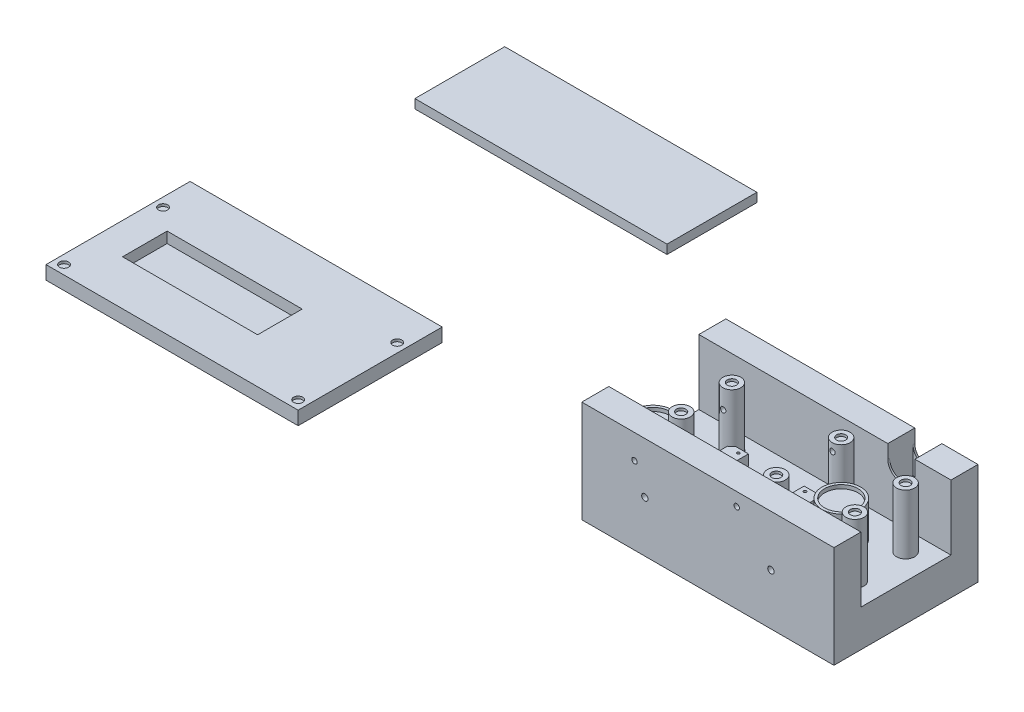
SolidWorks part; units mm, degrees
ref_plane "Front Plane" through (0, 0, 0) normal (0, 0, 1) x (1, 0, 0)
ref_plane "Top Plane" through (0, 0, 0) normal (0, 1, 0) x (1, 0, 0)
ref_plane "Right Plane" through (0, 0, 0) normal (1, 0, 0) x (0, 0, -1)
sketch "Sketch1" plane through (0, 0, 0) normal (0, 1, 0) x (1, 0, 0)
  line L1 (-125, -50) -> (125, -50)
  line L2 (-125, -50) -> (-125, 50)
  line L3 (-125, 50) -> (125, 50)
  line L4 (125, -50) -> (125, 50)
  line L5 (0, 50) -> (0, -50) construction
  line L6 (-125, 0) -> (125, 0) construction
  line L7 (-87.9863, 22.88) -> (-72.79, 22.88)
  line L8 (-91.88, 19.2734) -> (-91.88, -19.2734)
  line L9 (-87.9863, -22.88) -> (-72.79, -22.88)
  line L10 (-72.79, 22.88) -> (-72.79, -22.88)
  line L11 (-10.96, 22.88) -> (8.13, 22.88)
  line L12 (-10.96, 22.88) -> (-10.96, -22.88)
  line L13 (-10.96, -22.88) -> (8.13, -22.88)
  line L14 (8.13, 22.88) -> (8.13, -22.88)
  circle A0 centre (-96.485, 28.15) radius 10
  circle A1 centre (-96.485, -28.15) radius 10
  circle A2 centre (96.485, 28.15) radius 10
  circle A3 centre (96.485, -28.15) radius 10
  circle A4 centre (48.387, 4.8142) radius 21.5
  circle A5 centre (48.387, 4.8142) radius 18.55
  circle A6 centre (-96.485, 28.15) radius 5.17
  circle A7 centre (-96.485, -28.15) radius 5.17
  circle A8 centre (96.485, 28.15) radius 5.17
  circle A9 centre (96.485, -28.15) radius 5.17
  circle A10 centre (-96.485, 28.15) radius 10.5
  circle A11 centre (-96.485, -28.15) radius 10.5
  circle A12 centre (96.485, 28.15) radius 10.5
  circle A13 centre (96.485, -28.15) radius 10.5
  point P0 (0, 0)
  dimension "D3" = 20
  dimension "D6" = 53.46
  dimension "D8" = 43
  dimension "D9" = 37.1
  dimension "D15" = 10.34
  dimension "D16" = 21
  dimension "D17" = 10.34
  dimension "D1" = 250
  dimension "D2" = 100
  dimension "D4" = 192.97
  dimension "D5" = 56.3
  dimension "D7" = 58.31
  dimension "D10" = 19.09
  dimension "D11" = 45.76
  dimension "D12" = 33.12
  dimension "D13" = 114.04
  dimension "D14" = 19.09
extrude "Boss-Extrude1" add sketch "Sketch1" against normal blind 41 contours L1 L4 L3 L2
extrude "Boss-Extrude2" add sketch "Sketch1<4>" along normal blind 12 contours A1 L9 L10 L7 A0 L8 | L14 L11 L12 L13 region at (-82.1271, 0, 0) region at (-1.415, 0, 0)
sketch "Sketch1<4>" plane through (0, 0, 0) normal (0, 1, 0) x (1, 0, 0) same geometry as "Sketch1"
extrude "Boss-Extrude3" add sketch "Sketch1<5>" along normal blind 39 contours A4 A5 region at (27.4951, 0, -4.8142)
sketch "Sketch1<5>" plane through (0, 0, 0) normal (0, 1, 0) x (1, 0, 0) same geometry as "Sketch1"
extrude "Boss-Extrude4" add sketch "Sketch1<6>" along normal blind 34.9 contours A5
sketch "Sketch1<6>" plane through (0, 0, 0) normal (0, 1, 0) x (1, 0, 0) same geometry as "Sketch1"
extrude "Cut-Extrude1" cut sketch "Sketch1<9>" against normal blind 5 contours L8 A11 L9 A1 | A1 A7 | A7 | L7 A10 L8 A0 | A0 A6 | A6 | L9 A11 L8 A1 | L8 A10 L7 A0 region at (-86.582, 0, -25.3288) region at (-89.5989, 0, -20.7343) region at (-89.8817, 0, -21.0212) region at (-89.5989, 0, 20.7343) region at (-92.177, 0, 18.9935) region at (-89.8817, 0, 21.0212) region at (-96.485, 0, -28.15) region at (-96.485, 0, 28.15)
sketch "Sketch1<9>" plane through (0, 0, 0) normal (0, 1, 0) x (1, 0, 0) same geometry as "Sketch1"
extrude "Boss-Extrude7" add sketch "Sketch1<10>" along normal blind 66.2 contours A3 A9 | A9 | A2 A8 | A8 | A3 region at (86.7678, 0, -28.15) region at (86.7678, 0, 28.15) region at (96.485, 0, -28.15) region at (96.485, 0, 28.15)
sketch "Sketch1<10>" plane through (0, 0, 0) normal (0, 1, 0) x (1, 0, 0) same geometry as "Sketch1"
extrude "Boss-Extrude8" add sketch "Sketch1<11>" along normal blind 66.2 and the other way up to surface (5 mm away) separate body contours A1 A7 | A7 | A6 | A0 A6 region at (-89.8817, 0, -21.0212) region at (-89.8817, 0, 21.0212) region at (-96.485, 0, -28.15) region at (-96.485, 0, 28.15) other way up to face at (-96.485, -5, -17.65)
sketch "Sketch1<11>" plane through (0, 0, 0) normal (0, 1, 0) x (1, 0, 0) same geometry as "Sketch1"
extrude "Cut-Extrude2" cut sketch "Sketch1<12>" against normal blind 2.75 from surface contours A7 | A6 | A9 | A8 starting at face at (-96.485, 66.2, -18.15)
sketch "Sketch1<12>" plane through (0, 0, 0) normal (0, 1, 0) x (1, 0, 0) same geometry as "Sketch1"
sketch "Sketch3" plane through (0, 12, 0) normal (0, 1, 0) x (1, 0, 0)
  circle A0 centre (-79.2548, 18.1338) radius 1.5
  circle A1 centre (-79.2548, 0.1338) radius 1.5
  circle A2 centre (-5.2548, 18.1338) radius 1.5
  circle A3 centre (-5.2548, 0.1338) radius 1.5
  dimension "D1" = 3
  dimension "D2" = 18
  dimension "D3" = 74
  dimension "D4" = 8.02
  dimension "D5" = 19.93
extrude "Cut-Extrude3" cut sketch "Sketch3" against normal blind 12
sketch "Sketch4" plane through (0, -41, 0) normal (0, -1, 0) x (1, 0, 0)
  line L1 (-120, 30) -> (-39.4754, 30)
  line L2 (-120, 30) -> (-120, -19.5)
  line L3 (-120, -19.5) -> (30, -19.5)
  line L4 (30, 30) -> (30, -19.5)
  line L5 (-125, 50) -> (-125, -50) construction
  line L6 (-125, 50) -> (125, 50) construction
  line L7 (-15.8404, 30) -> (30, 30)
  arc A0 (-15.8404, 30) -> (-39.4754, 30) centre (-27.6579, 30) ccw
  dimension "D1" = 150
  dimension "D2" = 49.5
  dimension "D3" = 20
  dimension "D4" = 5
extrude "Cut-Extrude4" cut sketch "Sketch4" against normal blind 31 contours L1 A0 L7 L4 L3 L2
sketch "Sketch5" plane through (-125, 0, 0) normal (-1, 0, 0) x (0, 0, 1)
  line L0 (-50, 0) -> (-50, -41)
  line L1 (-50, -41) -> (50, -41)
  line L2 (50, -41) -> (50, 0)
  line L3 (50, 0) -> (-50, 0)
extrude "Boss-Extrude9" add sketch "Sketch5" along normal blind 30
sketch "Sketch6" plane through (0, 0, 0) normal (0, 1, 0) x (1, 0, 0)
  line L0 (-130.5, -25.5) -> (-130.5, -47) construction
  line L1 (-155, -50) -> (125, -50) construction
  line L2 (-130.5, -25.5) -> (-155, -25.5) construction
  line L3 (-155, -50) -> (-155, 50) construction
  line L4 (-130.5, -25.5) -> (-152, -25.5) construction
  circle A0 centre (-130.5, -25.5) radius 21.5
  circle A1 centre (-130.5, -25.5) radius 18.55
  dimension "D1" = 43
  dimension "D2" = 37.1
  dimension "D3" = 3
  dimension "D4" = 3
extrude "Boss-Extrude10" add sketch "Sketch6" along normal blind 39
sketch "Sketch7" plane through (0, 0, 0) normal (0, 1, 0) x (1, 0, 0)
  circle A0 centre (-130.5, -25.5) radius 18.55
extrude "Boss-Extrude11" add sketch "Sketch7" along normal blind 35
sketch "Sketch8" plane through (-155, 0, 0) normal (-1, 0, 0) x (0, 0, 1)
  line L0 (4, 30.377) -> (4, -41) construction
  line L1 (4, 39) -> (4, 0) construction
  line L2 (-50, -41) -> (50, -41) construction
  line L3 (50, -41) -> (50, 0) construction
  line L4 (47, 20.3949) -> (47, -41) construction
  line L5 (47, 0) -> (47, 39) construction
  dimension "D1" = 46
  dimension "D2" = 3
sketch "Sketch10" plane through (0, 0, 0) normal (0, 1, 0) x (1, 0, 0)
  line L0 (-155, 0) -> (125, 0) construction
  line L1 (-155, -50) -> (-155, 50) construction
  line L2 (125, -50) -> (125, 50) construction
  line L3 (17, -36) -> (17, -46) construction
  line L4 (-155, -50) -> (125, -50) construction
  circle A0 centre (17, -36) radius 10
  circle A1 centre (17, 36) radius 10
  circle A2 centre (17, -36) radius 5.09
  circle A3 centre (17, 36) radius 5.09
  dimension "D1" = 20
  dimension "D4" = 10.18
  dimension "D2" = 4
  dimension "D3" = 108
extrude "Boss-Extrude12" add sketch "Sketch10" along normal blind 66.2
sketch "Sketch11" plane through (0, 0, 0) normal (0, 1, 0) x (1, 0, 0)
  circle A0 centre (17, -36) radius 5.17
  circle A1 centre (17, 36) radius 5.17
  dimension "D1" = 10.34
  dimension "D2" = 10.34
extrude "Boss-Extrude13" add sketch "Sketch11" along normal blind 63.45
sketch "Sketch9" plane through (0, 0, 50) normal (0, 0, 1) x (1, 0, 0)
  line L0 (-96.485, 66.2) -> (-96.485, 0) construction
  line L1 (-86.485, 66.2) -> (-106.485, 66.2) construction
  line L2 (-155, 0) -> (125, 0) construction
  line L3 (-96.485, 0) -> (-96.485, 45) construction
  line L4 (-96.485, 0) -> (-96.485, 57.6) construction
  line L5 (17, 66.2) -> (17, 0) construction
  line L6 (22.09, 66.2) -> (11.91, 66.2) construction
  line L7 (17, 0) -> (17, 57.6) construction
  circle A0 centre (-96.485, 45) radius 3
  circle A1 centre (17, 57.6) radius 3
  dimension "D2" = 6
  dimension "D5" = 6
  dimension "D1" = 45
  dimension "D3" = 57.6
  dimension "D4" = 57.6
extrude "Cut-Extrude5" cut sketch "Sketch9" against normal through all both and the other way through all
sketch "Sketch15" plane through (0, 0, 50) normal (0, 0, 1) x (1, 0, 0)
  line L0 (-155, 15.6) -> (125, 15.6) construction
  line L1 (-155, -41) -> (125, -41)
  line L2 (-155, -41) -> (-155, 72.2)
  line L3 (-155, 72.2) -> (125, 72.2)
  line L4 (125, -41) -> (125, 72.2)
  line L6 (-155, 15.6) -> (-85, 15.6) construction
  line L7 (-85, 15.6) -> (55, 15.6) construction
  circle A0 centre (-85, 15.6) radius 3.5
  circle A1 centre (55, 15.6) radius 3.5
  dimension "D5" = 7
  dimension "D6" = 7
  dimension "D1" = 113.2
  dimension "D2" = 280
  dimension "D3" = 70
  dimension "D4" = 140
extrude "Boss-Extrude17" add sketch "Sketch15" along normal blind 30
sketch "Sketch20" plane through (0, 0, 0) normal (0, 1, 0) x (1, 0, 0)
  line L0 (-605.7799, 235.3036) -> (-325.7799, 235.3036) construction
  line L1 (-605.7799, 285.3036) -> (-325.7799, 285.3036)
  line L2 (-605.7799, 285.3036) -> (-605.7799, 185.3036)
  line L3 (-605.7799, 185.3036) -> (-325.7799, 185.3036)
  line L4 (-325.7799, 285.3036) -> (-325.7799, 185.3036)
  circle A0 centre (-547.2649, 263.4536) radius 5.05
  circle A1 centre (-547.2649, 263.4536) radius 10.05
  circle A2 centre (-433.7799, 271.3036) radius 5.05
  circle A3 centre (-433.7799, 271.3036) radius 10.05
  circle A4 centre (-354.2949, 263.4536) radius 5.05
  circle A5 centre (-354.2949, 263.4536) radius 10.05
  circle A6 centre (-547.2649, 207.1536) radius 5.05
  circle A7 centre (-547.2649, 207.1536) radius 10.05
  circle A8 centre (-433.7799, 199.3036) radius 5.05
  circle A9 centre (-433.7799, 199.3036) radius 10.05
  circle A10 centre (-354.2949, 207.1536) radius 5.05
  circle A11 centre (-354.2949, 207.1536) radius 10.05
  circle A12 centre (-581.2799, 209.8036) radius 18.55
  circle A13 centre (-402.3929, 240.1179) radius 18.55
  dimension "D1" = 10.1
  dimension "D2" = 20.1
  dimension "D3" = 10.1
  dimension "D4" = 20.1
  dimension "D5" = 10.1
  dimension "D6" = 20.1
  dimension "D7" = 37.1
  dimension "D8" = 37.1
extrude "Boss-Extrude18" add sketch "Sketch20" against normal blind 4 separate body contours L2 L0 A13 L4 L1 A1 A3 A5 | L0 L2 L3 L4 A13 A12 A7 A9 A11 region at (-471.0616, 0, -260.7215) region at (-458.7027, 0, -210.2185)
sketch "Sketch21" plane through (0, 0, 0) normal (0, 1, 0) x (1, 0, 0)
  line L0 (-605.7799, 235.3036) -> (-325.7799, 235.3036) construction
  line L1 (-605.7799, 285.3036) -> (-605.7799, 185.3036) construction
  line L2 (-325.7799, 285.3036) -> (-325.7799, 185.3036) construction
  line L4 (-605.7799, 285.3036) -> (-325.7799, 285.3036)
  line L5 (-605.7799, 285.3036) -> (-605.7799, 185.3036)
  line L6 (-605.7799, 185.3036) -> (-325.7799, 185.3036)
  line L7 (-325.7799, 285.3036) -> (-325.7799, 185.3036)
  circle A0 centre (-547.2649, 263.4536) radius 5.17
  circle A1 centre (-433.7799, 271.3036) radius 5.17
  circle A2 centre (-354.2949, 263.4536) radius 5.17
  circle A3 centre (-354.2949, 207.1536) radius 5.17
  circle A4 centre (-433.7799, 199.3036) radius 5.17
  circle A5 centre (-547.2649, 207.1536) radius 5.17
  dimension "D1" = 10.34
  dimension "D2" = 10.34
  dimension "D3" = 10.34
  dimension "D4" = 10.34
  dimension "D5" = 10.34
  dimension "D6" = 10.34
extrude "Boss-Extrude19" add sketch "Sketch21" along normal blind 2.75
sketch "Sketch22" plane through (0, 2.75, 0) normal (0, 1, 0) x (1, 0, 0)
  line L1 (-605.7799, 285.3036) -> (-325.7799, 285.3036)
  line L2 (-605.7799, 285.3036) -> (-605.7799, 185.3036)
  line L3 (-605.7799, 185.3036) -> (-325.7799, 185.3036)
  line L4 (-325.7799, 285.3036) -> (-325.7799, 185.3036)
extrude "Boss-Extrude20" add sketch "Sketch22" along normal blind 3.25
sketch "Sketch23" plane through (0, -41, 0) normal (0, -1, 0) x (1, 0, 0)
  circle A0 centre (-27.6579, 30) radius 11.8175
sketch "Sketch24" plane through (0, -41, 0) normal (0, -1, 0) x (1, 0, 0)
  circle A0 centre (-27.6579, 30) radius 11.8175
extrude "Cut-Extrude9" cut sketch "Sketch24" against normal through all both and the other way through all
sketch "Sketch25" plane through (0, -41, 0) normal (0, -1, 0) x (1, 0, 0)
  line L0 (-155, 80) -> (-155, -50) construction
  line L1 (-155, 80) -> (125, 80)
  line L2 (-155, 80) -> (-155, -50)
  line L3 (-155, -50) -> (125, -50)
  line L4 (125, 80) -> (125, -50)
  line L5 (-120, 30) -> (30, 30)
  line L6 (-120, 30) -> (-120, -19.5)
  line L7 (-120, -19.5) -> (30, -19.5)
  line L8 (30, 30) -> (30, -19.5)
  line L9 (-15, -50) -> (-15, 80) construction
  line L10 (-155, 15) -> (125, 15) construction
  circle A0 centre (-145, 70) radius 5.17
  circle A1 centre (-145, -40) radius 5.17
  circle A2 centre (115, -40) radius 5.17
  circle A3 centre (115, 70) radius 5.17
  dimension "D1" = 10.34
  dimension "D2" = 10
  dimension "D4" = 10.34
  dimension "D5" = 10.34
  dimension "D6" = 10.34
  dimension "D3" = 10
extrude "Cut-Extrude10" cut sketch "Sketch25" against normal blind 2.75 and the other way through all contours A1 | A3 | A2 | A0 region at (-145, -41, 70) region at (-145, -41, -40) region at (115, -41, -40) region at (115, -41, 70)
sketch "Sketch27" plane through (0, -41, 0) normal (0, -1, 0) x (1, 0, 0)
  line L0 (-697.9163, 132.1026) -> (-697.9163, 2.1026) construction
  line L1 (-697.9163, 132.1026) -> (-417.9163, 132.1026)
  line L2 (-697.9163, 132.1026) -> (-697.9163, 2.1026)
  line L3 (-697.9163, 2.1026) -> (-417.9163, 2.1026)
  line L4 (-417.9163, 132.1026) -> (-417.9163, 2.1026)
  line L5 (-662.9163, 82.1026) -> (-512.9163, 82.1026)
  line L6 (-662.9163, 82.1026) -> (-662.9163, 32.6026)
  line L7 (-662.9163, 32.6026) -> (-512.9163, 32.6026)
  line L8 (-512.9163, 82.1026) -> (-512.9163, 32.6026)
  line L9 (-557.9163, 2.1026) -> (-557.9163, 132.1026) construction
  line L10 (-697.9163, 67.1026) -> (-417.9163, 67.1026) construction
  circle A0 centre (-687.9163, 122.1026) radius 5.05
  circle A1 centre (-687.9163, 12.1026) radius 5.05
  circle A2 centre (-427.9163, 12.1026) radius 5.05
  circle A3 centre (-427.9163, 122.1026) radius 5.05
  dimension "D1" = 10.1
  dimension "D2" = 10
  dimension "D3" = 10
extrude "Boss-Extrude21" add sketch "Sketch27" along normal blind 2.75 separate body
sketch "Sketch28" plane through (0, -43.75, 0) normal (0, -1, 0) x (1, 0, 0)
  line L1 (-697.9163, 132.1026) -> (-417.9163, 132.1026)
  line L2 (-697.9163, 132.1026) -> (-697.9163, 2.1026)
  line L3 (-697.9163, 2.1026) -> (-417.9163, 2.1026)
  line L4 (-417.9163, 132.1026) -> (-417.9163, 2.1026)
  line L5 (-662.9163, 82.1026) -> (-512.9163, 82.1026)
  line L6 (-662.9163, 82.1026) -> (-662.9163, 32.6026)
  line L7 (-662.9163, 32.6026) -> (-512.9163, 32.6026)
  line L8 (-512.9163, 82.1026) -> (-512.9163, 32.6026)
extrude "Boss-Extrude22" add sketch "Sketch28" along normal blind 9.25
sketch "Sketch29" plane through (0, -53, 0) normal (0, -1, 0) x (1, 0, 0)
  line L1 (-697.9163, 132.1026) -> (-417.9163, 132.1026)
  line L2 (-697.9163, 132.1026) -> (-697.9163, 2.1026)
  line L3 (-697.9163, 2.1026) -> (-417.9163, 2.1026)
  line L4 (-417.9163, 132.1026) -> (-417.9163, 2.1026)
extrude "Boss-Extrude23" add sketch "Sketch29" along normal blind 3
sketch "Sketch31" plane through (0, 0, -50) normal (0, 0, -1) x (-1, 0, 0)
  line L0 (-69.887, 39) -> (-69.887, 0) construction
  line L1 (-125, 72.2) -> (-84.937, 72.2)
  line L2 (-125, 72.2) -> (-125, -41)
  line L3 (-125, -41) -> (155, -41)
  line L4 (155, 72.2) -> (155, -41)
  line L5 (-84.937, 57.15) -> (-84.937, 72.2) construction
  line L6 (-69.887, 39) -> (-69.887, 72.2) construction
  line L7 (-69.887, 72.2) -> (-69.887, 57.15) construction
  line L8 (-54.837, 57.15) -> (-54.837, 72.2) construction
  line L9 (-84.937, 57.15) -> (-84.937, 72.2)
  line L10 (-54.837, 57.15) -> (-54.837, 72.2)
  line L11 (-54.837, 72.2) -> (155, 72.2)
  arc A0 (-84.937, 57.15) -> (-54.837, 57.15) centre (-69.887, 57.15) ccw
  dimension "D1" = 15.05
  dimension "D2" = 30.1
sketch "Sketch33" plane through (0, 0, 80) normal (0, 0, 1) x (1, 0, 0)
  circle A0 centre (-96.485, 45) radius 3
  circle A1 centre (17, 57.6) radius 3
  dimension "D1" = 6
  dimension "D2" = 6
extrude "Cut-Extrude11" cut sketch "Sketch33" against normal blind 130
sketch "Sketch34" plane through (-155, 0, 0) normal (-1, 0, 0) x (0, 0, 1)
  line L1 (4, -41) -> (4, -25.5) construction
  line L2 (4, 30.377) -> (4, -41) construction
  circle A0 centre (4, -25.5) radius 3
  dimension "D2" = 6
  dimension "D1" = 15.5
extrude "Cut-Extrude12" cut sketch "Sketch34" against normal blind 40
extrude "Boss-Extrude24" add sketch "Sketch31" along normal blind 30
sketch "Sketch35" plane through (0, 72.2, 0) normal (0, 1, 0) x (1, 0, 0)
  line L0 (69.887, 50) -> (69.887, 80) construction
  line L1 (54.837, 50) -> (84.937, 50) construction
  line L2 (84.937, 80) -> (54.837, 80) construction
  line L3 (69.887, 50) -> (69.887, 52) construction
  line L4 (69.887, 52) -> (54.837, 52)
  line L5 (54.837, 80) -> (54.837, 50) construction
  line L6 (54.837, 52) -> (54.837, 78)
  line L8 (84.937, 80) -> (84.937, 50) construction
  line L9 (84.937, 80) -> (84.937, 52)
  line L10 (84.937, 80) -> (84.937, 50) construction
  line L11 (84.937, 52) -> (69.887, 52)
  line L12 (54.837, 78) -> (84.937, 78)
  line L13 (84.937, 78) -> (84.937, 52)
  dimension "D1" = 2
  dimension "D2" = 26
extrude "Cut-Extrude13" cut sketch "Sketch35" against normal blind 45 contours L12 L6 L4 L11 L9 region at (69.887, 72.2, -65)
sketch "Sketch36" plane through (0, 0, 2.1026) normal (0, 0, -1) x (-1, 0, 0)
  line L1 (417.9163, -41) -> (697.9163, -41)
  line L2 (417.9163, -41) -> (417.9163, -56)
  line L3 (417.9163, -56) -> (697.9163, -56)
  line L4 (697.9163, -41) -> (697.9163, -56)
extrude "Boss-Extrude25" add sketch "Sketch36" along normal blind 30
sketch "Sketch37" plane through (0, 0, -185.3036) normal (0, 0, 1) x (1, 0, 0)
  line L1 (-605.7799, 6) -> (-325.7799, 6)
  line L2 (-605.7799, 6) -> (-605.7799, -4)
  line L3 (-605.7799, -4) -> (-325.7799, -4)
  line L4 (-325.7799, 6) -> (-325.7799, -4)
extrude "Cut-Extrude14" cut sketch "Sketch37" against normal blind 0.1
sketch "Sketch38" plane through (0, 0, -285.3036) normal (0, 0, -1) x (-1, 0, 0)
  line L1 (325.7799, 6) -> (605.7799, 6)
  line L2 (325.7799, 6) -> (325.7799, -4)
  line L3 (325.7799, -4) -> (605.7799, -4)
  line L4 (605.7799, 6) -> (605.7799, -4)
extrude "Cut-Extrude15" cut sketch "Sketch38" against normal blind 0.1
sketch "Sketch39" plane through (0, 72.2, 0) normal (0, 1, 0) x (1, 0, 0)
  line L0 (-96.485, 38.65) -> (-96.485, -38.65) construction
  circle A0 centre (-96.485, 28.15) radius 10.5 construction
  arc A1 (-87.4033, 22.88) -> (-91.88, 18.7137) centre (-96.485, 28.15) ccw construction
  circle A2 centre (-96.485, -28.15) radius 10.5 construction
